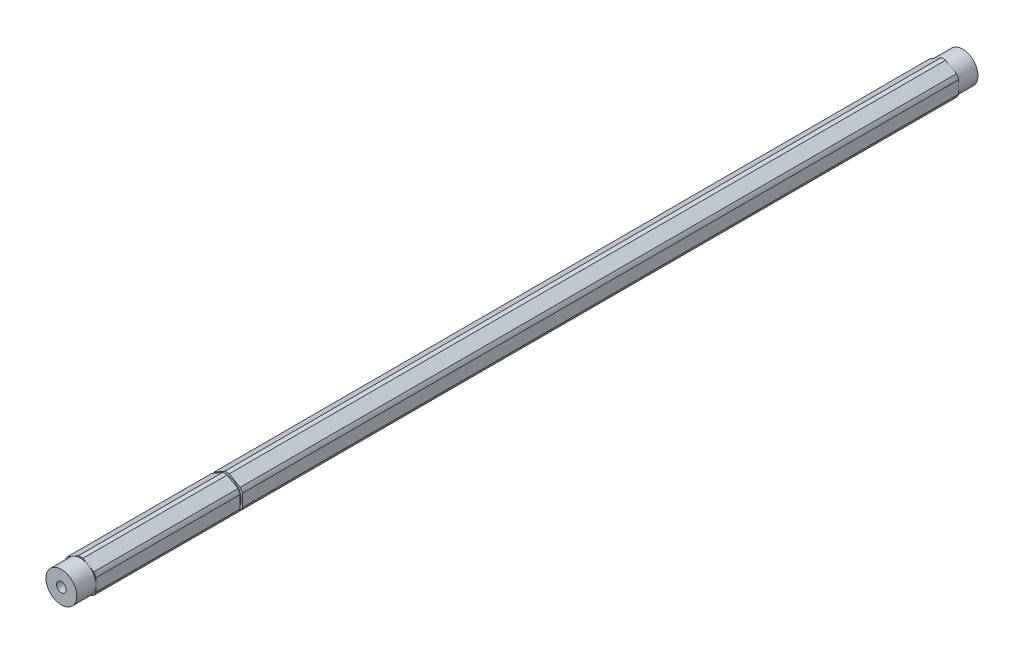
SolidWorks part; units mm, degrees
ref_plane "Front Plane" through (0, 0, 0) normal (0, 0, 1) x (1, 0, 0)
ref_plane "Top Plane" through (0, 0, 0) normal (0, 1, 0) x (1, 0, 0)
ref_plane "Right Plane" through (0, 0, 0) normal (1, 0, 0) x (0, 0, -1)
sketch "Sketch1" plane through (0, 0, 0) normal (0, 0, 1) x (1, 0, 0)
  line L1 (0, 7.3323) -> (-6.35, 3.6662)
  line L2 (-6.35, 3.6662) -> (-6.35, -3.6662)
  line L3 (-6.35, -3.6662) -> (0, -7.3323)
  line L4 (0, -7.3323) -> (6.35, -3.6662)
  line L5 (6.35, -3.6662) -> (6.35, 3.6662)
  line L6 (6.35, 3.6662) -> (0, 7.3323)
  circle A0 centre (0, 0) radius 6.35 construction
  circle A1 centre (0, 0) radius 2
  circle A2 centre (0, 0) radius 6.858
  dimension "D1" = 12.7
  dimension "D2" = 4
  dimension "D3" = 13.716
extrude "Boss-Extrude1" add sketch "Sketch1" along normal mid plane 355.6 contours L5 A2 L6 L1 L2 L3 L4 A1 region at (0, 6.6711, 0)
sketch "Sketch3" plane through (0, 0, 177.8) normal (0, 0, 1) x (1, 0, 0)
  circle A0 centre (0, 0) radius 6.35
  circle A1 centre (0, 0) radius 2
  circle A2 centre (0, 0) radius 5.8547 construction
  point P5 (0, 5.8547)
  dimension "D1" = 12.7
  dimension "D2" = 4
  dimension "D3" = 11.7094
extrude "Boss-Extrude3" add sketch "Sketch3" along normal blind 7.9375
mirror "Mirror1" about plane through (0, 0, 0) normal (0, 0, 1) of "Boss-Extrude3"
sketch "Sketch5" plane through (0, 0, 0) normal (1, 0, 0) x (0, 0, -1)
  line L0 (-177.8, 5.8547) -> (-117.475, 5.8547) construction
  line L1 (-118.364, 6.858) -> (-117.475, 6.858)
  line L2 (-118.364, 6.858) -> (-118.364, 5.8547)
  line L3 (-118.364, 5.8547) -> (-117.475, 5.8547)
  line L4 (-117.475, 6.858) -> (-117.475, 5.8547)
  line L5 (-177.8, 5.8547) -> (-177.8, -5.8547) construction
  line L8 (0, 0) -> (14.4053, 0) construction
  point P11 (-119.0636, 5.8547)
  dimension "D1" = 0.889
  dimension "D2" = 6.858
  dimension "D3" = 59.436
revolve "Cut-Revolve1" cut sketch "Sketch5" angle 360 about L8
equation "\"D2@Sketch1\"=4mm"
